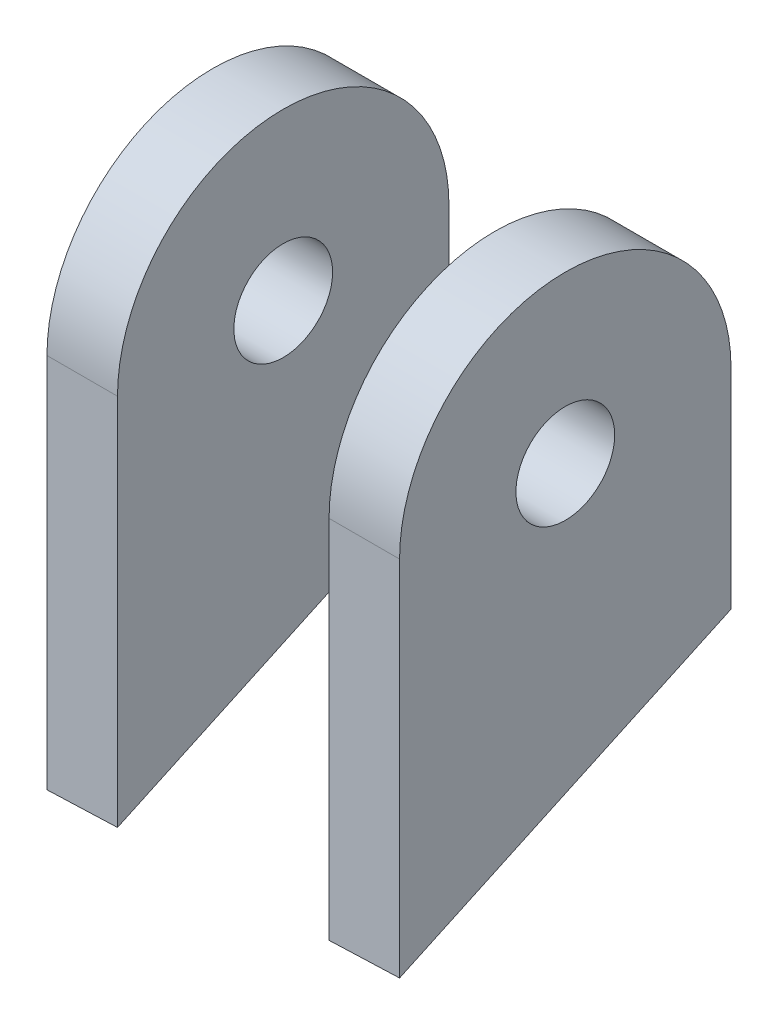
SolidWorks part; units mm, degrees
ref_plane "前视基准面" through (0, 0, 0) normal (0, 0, 1) x (1, 0, 0)
ref_plane "上视基准面" through (0, 0, 0) normal (0, 1, 0) x (1, 0, 0)
ref_plane "右视基准面" through (0, 0, 0) normal (1, 0, 0) x (0, 0, -1)
sketch "草图1" plane through (0, 0, 0) normal (1, 0, 0) x (0, 0, -1)
  line L1 (-23.5, 0) -> (-23.5, -107.177)
  line L2 (23.5, 0) -> (23.5, -107.177)
  line L3 (23.5, -107.177) -> (-23.5, -107.177)
  circle A0 centre (0, 0) radius 7
  arc A1 (23.5, 0) -> (-23.5, 0) centre (0, 0) ccw
extrude "凸台-拉伸1" add sketch "草图1" along normal blind 10 and the other way blind 40
extrude "切除-拉伸1" cut sketch "草图1<2>" against normal blind 30
sketch "草图1<2>" plane through (0, 0, 0) normal (1, 0, 0) x (0, 0, -1) same geometry as "草图1"
sketch "草图2" plane through (1.273, -33.6426, -15.601) normal (-0.0343, 0.9067, 0.4204) x (0.9994, 0.0311, 0.0144)
  circle A0 centre (0, 0) radius 285.3969
extrude "切除-拉伸2" cut sketch "草图2" against normal blind 284.6875
